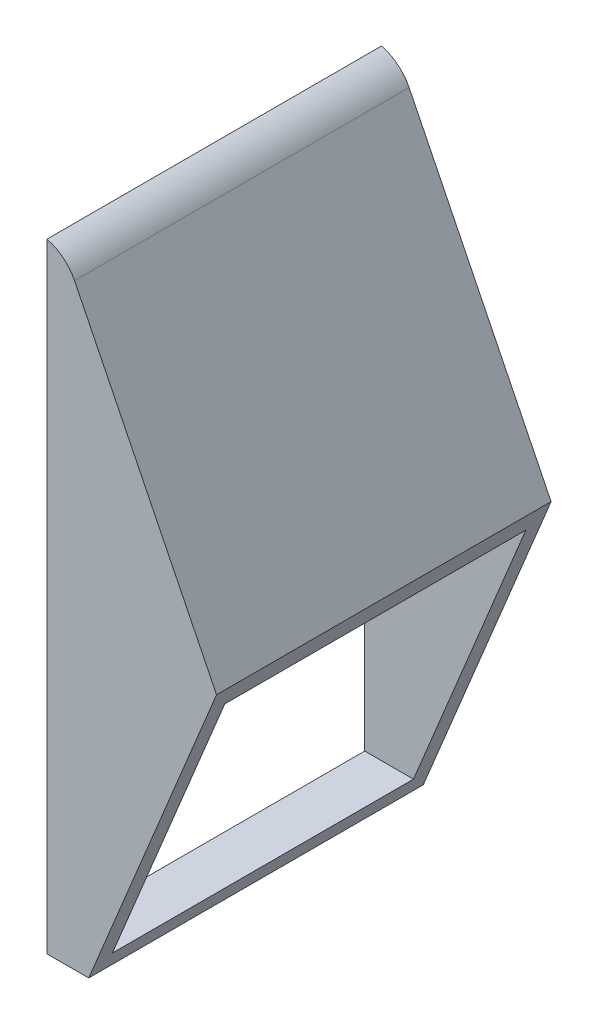
SolidWorks part; units mm, degrees
material "Custom Plastic"
ref_plane "X-Y Datum" through (0, 0, 0) normal (0, 0, 1) x (1, 0, 0)
ref_plane "X-Z Datum" through (0, 0, 0) normal (0, 1, 0) x (1, 0, 0)
ref_plane "Y-Z Datum" through (0, 0, 0) normal (1, 0, 0) x (0, 0, -1)
sketch "Sketch1" plane through (0, 0, 0) normal (0, 0, 1) x (1, 0, 0)
  line L0 (0, 0) -> (0, 74)
  line L1 (0, 0) -> (5, 0)
  line L3 (5, 0) -> (20.2812, 36.966)
  line L4 (0, 74) -> (2, 74)
  line L5 (2, 74) -> (20.2812, 36.966)
  dimension "D1" = 74
  dimension "D2" = 40
  dimension "D3" = 2
  dimension "D4" = 5
extrude "Boss-Extrude1" add sketch "Sketch1" against normal mid plane 40
shell "Shell1" thickness 2 removed face at (12.6406, 18.483, 0)
sketch "Sketch2" plane through (2, 0, 0) normal (1, 0, 0) x (0, 0, -1)
  line L4 (-18, 69.4817) -> (-18, 2)
  line L5 (-18, 2) -> (18, 2)
  line L6 (18, 2) -> (18, 69.4817)
  line L7 (18, 69.4817) -> (-18, 69.4817)
  line L8 (-18, 69.4817) -> (-18, 2)
  line L9 (-18, 2) -> (18, 2)
  line L10 (18, 2) -> (18, 69.4817)
  line L12 (18, 69.4817) -> (-18, 69.4817)
  dimension "D1" = 0
extrude "Cut-Extrude1" cut sketch "Sketch2" against normal through all
fillet "Fillet1" radius 20 1 edges at (2, 69.4817, 0)
fillet "Fillet3" radius 5 1 edges at (2, 74, 0)
